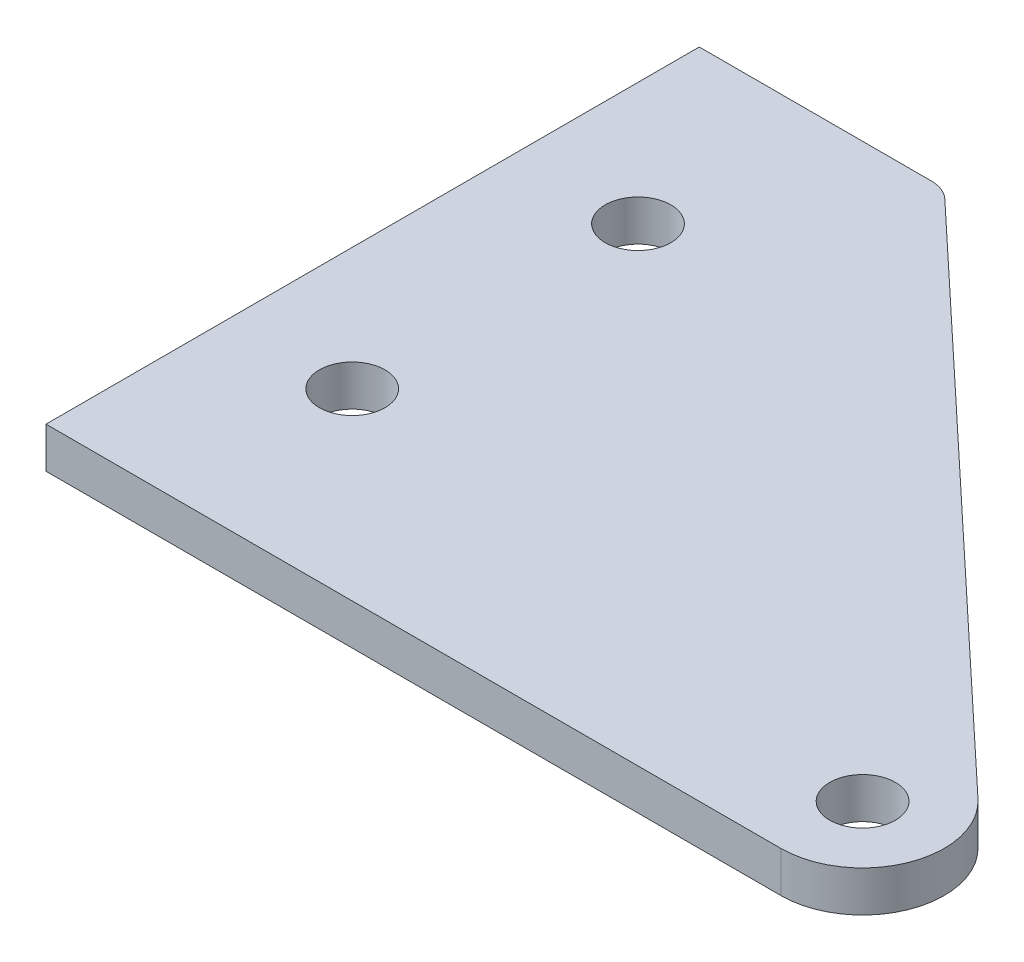
SolidWorks part; units mm, degrees
ref_plane "Front" through (0, 0, 0) normal (0, 0, 1) x (1, 0, 0)
ref_plane "Top" through (0, 0, 0) normal (0, 1, 0) x (1, 0, 0)
ref_plane "Right" through (0, 0, 0) normal (1, 0, 0) x (0, 0, -1)
sketch "Sketch1" plane through (0, 0, 0) normal (0, 1, 0) x (1, 0, 0)
  line L0 (0, 0) -> (0, 50.8)
  line L1 (0, 50.8) -> (19.05, 50.8)
  line L2 (0, 0) -> (57.15, 0)
  line L3 (19.05, 50.8) -> (61.4946, 10.9811)
  arc A0 (61.4946, 10.9811) -> (57.15, 0) centre (57.15, 6.35) cw
  point P7 (45.7913, 11.0494)
  point P8 (25.526, 14.0411)
  point P9 (44.8169, 9.6052)
  point P10 (45.7913, 10.121)
  point P11 (24.0818, 12.7)
  point P12 (45.6422, 5.08)
  point P13 (18.2017, 12.7)
  point P14 (12.3184, 19.05)
  point P15 (40.6406, 9.2909)
  point P16 (40.0151, 8.4048)
  point P17 (61.069, 12.8909)
  point P18 (15.6977, 50.8)
  point P19 (17.6466, 50.8)
  point P22 (21.701, 50.8)
  point P23 (61.3464, 10.4847)
  dimension "D1" = 50.8
  dimension "D2" = 57.15
  dimension "D3" = 6.35
  dimension "D4" = 19.05
extrude "Boss-Extrude1" add sketch "Sketch1" along normal blind 3.175
hole_wizard "1/4-20 Tapped Hole1" positions "Sketch4" profile "Sketch3" tap size "1/4-20" standard "ANSI Inch" end condition through all
sketch "Sketch4" plane through (0, 0, 0) normal (0, -1, 0) x (-1, 0, 0)
  point P0 (-57.15, 6.35)
  point P9 (-38.1, 4.445)
sketch "Sketch3" plane through (57.15, 0, -6.35) normal (1, 0, 0) x (0, 0, -1)
  line L0 (0, 0) -> (0, 3.175)
  line L1 (0, 3.175) -> (2.5527, 3.175)
  line L2 (2.5527, 3.175) -> (2.5527, 0)
  line L5 (2.5527, 0) -> (0, 0)
  line L11 (0, -6.35) -> (0, 107.95) construction
  dimension "Thru Tap Drill Dia." = 5.1054
  dimension "Thru Tap Drill Depth" = 3.175
cosmetic thread "Hole Thread1" parameters "D2"=6.35
hole_wizard "1/4-20 Tapped Hole2" positions "Sketch7" profile "Sketch8" tap size "1/4-20" standard "ANSI Inch" end condition through all
sketch "Sketch7" plane through (0, 3.175, 0) normal (0, 1, 0) x (1, 0, 0)
  line L4 (0, 0) -> (57.15, 0) construction
  line L7 (9.525, 50.8) -> (9.525, 0)
  line L8 (19.05, 50.8) -> (0, 50.8) construction
  point P0 (9.525, 36.5125)
  point P2 (9.525, 14.2875)
  dimension "D1" = 22.225
  dimension "D2" = 14.2875
sketch "Sketch8" plane through (9.525, 3.175, -36.5125) normal (1, 0, 0) x (0, 0, 1)
  line L0 (0, 0) -> (0, 3.175)
  line L1 (0, 3.175) -> (2.5527, 3.175)
  line L2 (2.5527, 3.175) -> (2.5527, 0)
  line L5 (2.5527, 0) -> (0, 0)
  line L11 (0, -6.35) -> (0, 107.95) construction
  dimension "Thru Tap Drill Dia." = 5.1054
  dimension "Thru Tap Drill Depth" = 3.175
cosmetic thread "Hole Thread2" parameters "D2"=6.35
cosmetic thread "Hole Thread3" parameters "D2"=6.35
fillet "Fillet1" radius 2.54 1 edges at (19.05, 1.5875, -50.8)
